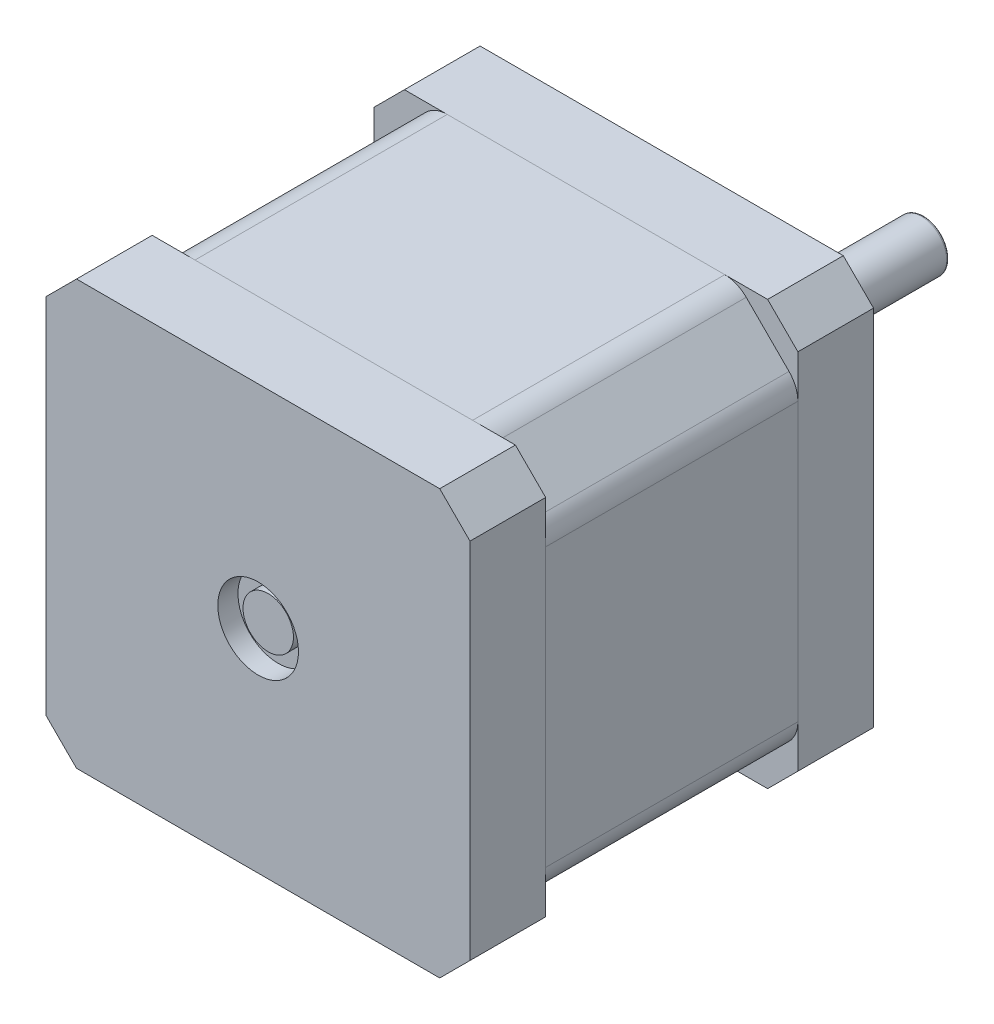
SolidWorks part; units mm, degrees
ref_plane "Ön Düzlem" through (0, 0, 0) normal (0, 0, 1) x (1, 0, 0)
ref_plane "Üst Düzlem" through (0, 0, 0) normal (0, 1, 0) x (1, 0, 0)
ref_plane "Sağ Düzlem" through (0, 0, 0) normal (1, 0, 0) x (0, 0, -1)
sketch "Çizim1" plane through (0, 0, 0) normal (0, 0, 1) x (1, 0, 0)
  line L0 (-15.8783, 20.121) -> (-20.121, 15.8783)
  line L1 (20.121, 15.8783) -> (15.8783, 20.121)
  line L2 (20.121, -15.8783) -> (15.8783, -20.121)
  line L3 (-15.8783, -20.121) -> (-20.121, -15.8783)
  line L4 (13.757, -20.9997) -> (-13.757, -20.9997)
  line L5 (20.9997, -13.757) -> (20.9997, 13.757)
  line L6 (13.757, 20.9997) -> (-13.757, 20.9997)
  line L7 (-20.9997, -13.757) -> (-20.9997, 13.757)
  line L9 (-15.5, -15.5) -> (15.5, -15.5) construction
  line L10 (-15.5, -15.5) -> (-15.5, 15.5) construction
  line L11 (-15.5, 15.5) -> (15.5, 15.5) construction
  line L12 (15.5, -15.5) -> (15.5, 15.5) construction
  line L13 (-15.5, -15.5) -> (15.5, 15.5) construction
  line L14 (-15.5, 15.5) -> (15.5, -15.5) construction
  arc A0 (-20.9997, 13.757) -> (-20.121, 15.8783) centre (-17.9997, 13.757) cw
  arc A1 (-15.8783, 20.121) -> (-13.757, 20.9997) centre (-13.757, 17.9997) cw
  arc A2 (13.757, 20.9997) -> (15.8783, 20.121) centre (13.757, 17.9997) cw
  arc A3 (20.121, 15.8783) -> (20.9997, 13.757) centre (17.9997, 13.757) cw
  arc A4 (20.9997, -13.757) -> (20.121, -15.8783) centre (17.9997, -13.757) cw
  arc A5 (15.8783, -20.121) -> (13.757, -20.9997) centre (13.757, -17.9997) cw
  arc A6 (-13.757, -20.9997) -> (-15.8783, -20.121) centre (-13.757, -17.9997) cw
  arc A7 (-20.121, -15.8783) -> (-20.9997, -13.757) centre (-17.9997, -13.757) cw
  circle A8 centre (-15.5, 15.5) radius 1.5
  circle A9 centre (15.5, 15.5) radius 1.5
  circle A10 centre (15.5, -15.5) radius 1.5
  circle A11 centre (-15.5, -15.5) radius 1.5
  point P6 (0, 0)
  point P28 (0, 20.9997)
  point P29 (0, -20.9997)
  dimension "D1" = 3
  dimension "D2" = 3
  dimension "D3" = 41.9993
  dimension "D7" = 3
  dimension "D8" = 3
  dimension "D9" = 3
  dimension "D10" = 3
  dimension "D4" = 41.9993
  dimension "D5" = 31
  dimension "D6" = 31
extrude "Yükseklik-Ekstrüzyon1" add sketch "Çizim1" along normal blind 25
sketch "Çizim2" plane through (0, 0, 0) normal (0, 0, -1) x (-1, 0, 0)
  line L0 (-21, 18) -> (-18, 21)
  line L1 (-18, -21) -> (18, -21)
  line L2 (-21, -18) -> (-21, 18)
  line L3 (-18, 21) -> (18, 21)
  line L4 (21, -18) -> (21, 18)
  line L5 (-21, -21) -> (21, 21) construction
  line L6 (-21, 21) -> (21, -21) construction
  line L7 (18, 21) -> (21, 18)
  line L8 (18, -21) -> (21, -18)
  line L9 (-21, -18) -> (-18, -21)
  circle A0 centre (-15.5, 15.5) radius 1.5
  circle A1 centre (15.5, 15.5) radius 1.5
  circle A2 centre (15.5, -15.5) radius 1.5
  circle A3 centre (-15.5, -15.5) radius 1.5
  point P0 (0, 0)
  dimension "D1" = 42
  dimension "D2" = 42
extrude "Yükseklik-Ekstrüzyon2" add sketch "Çizim2" along normal blind 7.5
sketch "Çizim3" plane through (0, 0, -7.5) normal (0, 0, -1) x (-1, 0, 0)
  circle A0 centre (0, 0) radius 11
  dimension "D1" = 22
extrude "Yükseklik-Ekstrüzyon3" add sketch "Çizim3" along normal blind 2
fillet "Radyus1" radius 1 1 edges at (11, 0, -7.5)
sketch "Çizim4" plane through (0, 0, -9.5) normal (0, 0, -1) x (-1, 0, 0)
  circle A0 centre (0, 0) radius 4
  dimension "D1" = 8
extrude "Kes-Ekstrüzyon2" cut sketch "Çizim4" against normal blind 2
sketch "Çizim5" plane through (0, 0, -7.5) normal (0, 0, -1) x (-1, 0, 0)
  circle A0 centre (0, 0) radius 2.5
  dimension "D1" = 5
extrude "Yükseklik-Ekstrüzyon4" add sketch "Çizim5" along normal blind 26
sketch "Çizim6" plane through (0, 0, -33.5) normal (0, 0, -1) x (-1, 0, 0)
  line L0 (-2.5, 0) -> (2, 0) construction
  line L1 (2, 2.1161) -> (2, -2.5)
  line L2 (2, -2.5) -> (3.2331, -2.5)
  line L3 (3.2331, -2.5) -> (3.2331, 2.1161)
  line L4 (3.2331, 2.1161) -> (2, 2.1161)
  circle A0 centre (0, 0) radius 2.5 construction
  circle A1 centre (0, 0) radius 2.5 construction
  point P10 (0, 0)
  dimension "D1" = 4.5
extrude "Kes-Ekstrüzyon3" cut sketch "Çizim6" against normal blind 17
fillet "Radyus2" radius 0.25 2 edges at (-2, 0, -33.5) (2.5, 0, -33.5)
sketch "Çizim7" plane through (0, 0, 25) normal (0, 0, 1) x (1, 0, 0)
  line L16 (-18, 21) -> (18, 21)
  line L17 (18, 21) -> (21, 18)
  line L18 (21, 18) -> (21, -18)
  line L19 (21, -18) -> (18, -21)
  line L20 (18, -21) -> (-18, -21)
  line L21 (-18, -21) -> (-21, -18)
  line L22 (-21, -18) -> (-21, 18)
  line L23 (-21, 18) -> (-18, 21)
extrude "Yükseklik-Ekstrüzyon5" add sketch "Çizim7" along normal blind 7.5
sketch "Çizim8" plane through (0, 0, 32.5) normal (0, 0, 1) x (1, 0, 0)
  circle A0 centre (0, 0) radius 4
  dimension "D1" = 8
extrude "Kes-Ekstrüzyon4" cut sketch "Çizim8" against normal blind 2
sketch "Çizim10" plane through (0, 0, 30.5) normal (0, 0, 1) x (1, 0, 0)
  circle A0 centre (0, 0) radius 2.5
  dimension "D1" = 5
extrude "Yükseklik-Ekstrüzyon7" add sketch "Çizim10" along normal blind 1
sketch "Çizim11" plane through (-20.9997, 0, 0) normal (-1, 0, 0) x (0, 0, 1)
  line L0 (12, 0) -> (-12, 0) construction
  line L1 (19, -10) -> (5, -10)
  line L2 (19, -10) -> (19, 10)
  line L3 (19, 10) -> (5, 10)
  line L4 (5, -10) -> (5, 10)
  line L5 (19, -10) -> (5, 10) construction
  line L6 (19, 10) -> (5, -10) construction
  line L7 (25, 13.757) -> (25, -13.757) construction
  point P0 (12, 0)
  dimension "D1" = 14
  dimension "D2" = 20
  dimension "D3" = 6
split line "Ayrım Çizgisi2"
sketch "Çizim12" plane through (-20.9997, 0, 0) normal (-1, 0, 0) x (0, 0, 1)
  line L0 (7.6653, -10) -> (7.6653, 10) construction
  line L1 (5, -10) -> (19, -10) construction
  line L2 (19, 10) -> (5, 10) construction
  text T0 "STEPPING MOTOR\r\nModel No: 17HS4401\r\nLot No:2017411\r\n17A  0.42N.M" font "Century Gothic" height in points 5
extrude "Yükseklik-Ekstrüzyon8" add sketch "Çizim12" along normal blind 0.1
